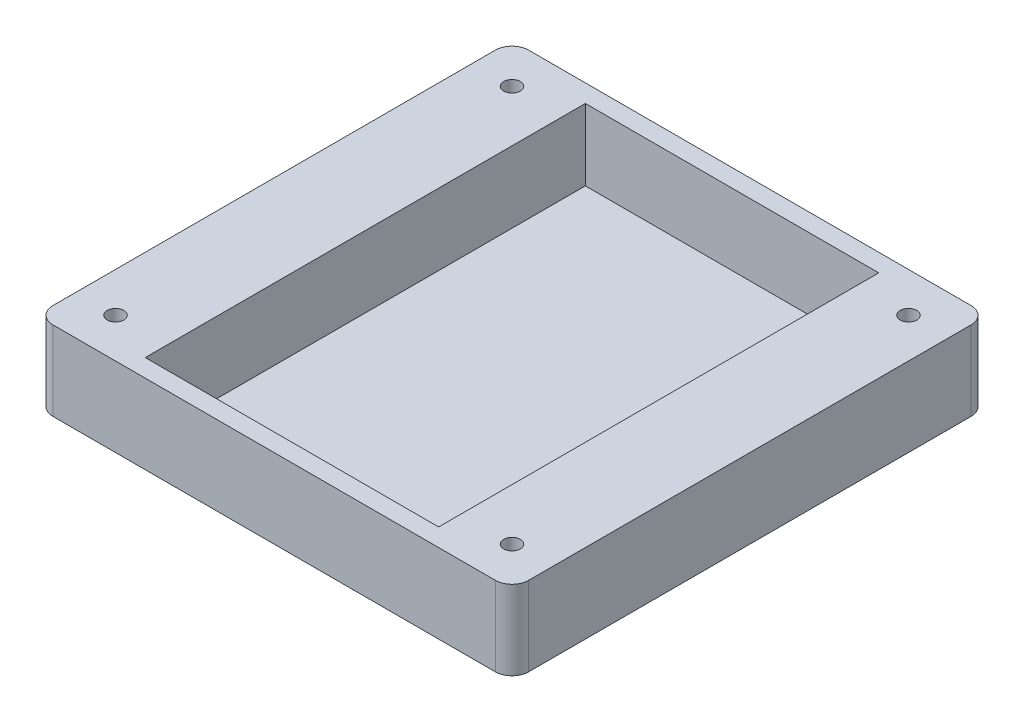
SolidWorks part; units mm, degrees
ref_plane "Front Plane" through (0, 0, 0) normal (0, 0, 1) x (1, 0, 0)
ref_plane "Top Plane" through (0, 0, 0) normal (0, 1, 0) x (1, 0, 0)
ref_plane "Right Plane" through (0, 0, 0) normal (1, 0, 0) x (0, 0, -1)
sketch "Sketch1" plane through (0, 0, 0) normal (0, 1, 0) x (1, 0, 0)
  line L0 (0, 0) -> (0, 26.0698) construction
  line L1 (-55.8, 60) -> (55.8, 60)
  line L2 (-60, 55.8) -> (-60, -55.8)
  line L3 (-55.8, -60) -> (55.8, -60)
  line L4 (60, 55.8) -> (60, -55.8)
  line L5 (-60, 60) -> (60, -60) construction
  line L6 (-60, -60) -> (60, 60) construction
  line L7 (-50, 50) -> (50, 50) construction
  line L8 (-50, 50) -> (-50, -50) construction
  line L9 (-50, -50) -> (50, -50) construction
  line L10 (50, 50) -> (50, -50) construction
  line L11 (-50, 50) -> (50, -50) construction
  line L12 (-50, -50) -> (50, 50) construction
  line L13 (0, 0) -> (27.008, 0) construction
  circle A0 centre (50, 50) radius 2.1
  circle A1 centre (-50, 50) radius 2.1
  circle A2 centre (50, -50) radius 2.1
  circle A3 centre (-50, -50) radius 2.1
  arc A4 (60, -55.8) -> (55.8, -60) centre (55.8, -55.8) cw
  arc A5 (-60, -55.8) -> (-55.8, -60) centre (-55.8, -55.8) ccw
  arc A6 (60, 55.8) -> (55.8, 60) centre (55.8, 55.8) ccw
  arc A7 (-60, 55.8) -> (-55.8, 60) centre (-55.8, 55.8) cw
  point P0 (0, 0)
  point P5 (0, 0)
  point P30 (50.4514, 50.4514)
  point P31 (53.0551, 44.8756)
  dimension "D4" = 4.2
  dimension "D5" = 4.2
  dimension "D1" = 120
  dimension "D2" = 120
  dimension "D3" = 100
extrude "Boss-Extrude1" add sketch "Sketch1" along normal blind 20
sketch "Sketch2" plane through (0, 20, 0) normal (0, 1, 0) x (1, 0, 0)
  line L1 (-37, 55.5) -> (37, 55.5)
  line L2 (-37, 55.5) -> (-37, -55.5)
  line L3 (-37, -55.5) -> (37, -55.5)
  line L4 (37, 55.5) -> (37, -55.5)
  line L5 (-37, 55.5) -> (37, -55.5) construction
  line L6 (-37, -55.5) -> (37, 55.5) construction
  point P0 (0, 0)
  dimension "D1" = 111
  dimension "D2" = 74
extrude "Cut-Extrude1" cut sketch "Sketch2" against normal blind 18
